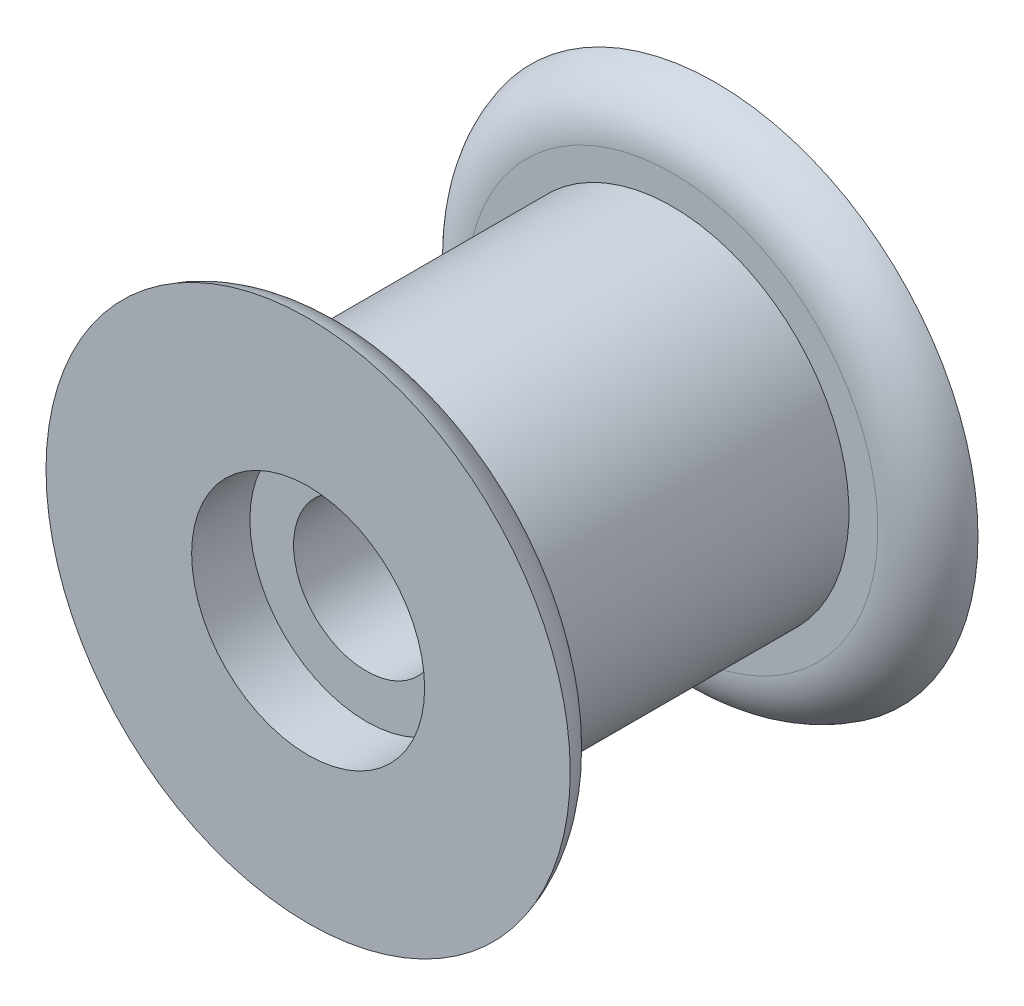
SolidWorks part; units mm, degrees
ref_plane "Front Plane" through (0, 0, 0) normal (0, 0, 1) x (1, 0, 0)
ref_plane "Top Plane" through (0, 0, 0) normal (0, 1, 0) x (1, 0, 0)
ref_plane "Right Plane" through (0, 0, 0) normal (1, 0, 0) x (0, 0, -1)
sketch "Sketch1" plane through (0, 0, 0) normal (0, 1, 0) x (1, 0, 0)
  line L0 (0, 0) -> (9, 0)
  line L1 (9, 0) -> (9, -1.5)
  line L2 (9, -1.5) -> (6.07, -1.5)
  line L3 (6.07, -1.5) -> (6.07, -12.5)
  line L4 (6.07, -12.5) -> (9, -12.5)
  line L5 (9, -12.5) -> (9, -14)
  line L6 (9, -14) -> (0, -14)
  line L7 (0, 9.9412) -> (0, -24.4941) construction
  line L8 (0, 0) -> (0, -14)
  dimension "D1" = 9
  dimension "D2" = 9
  dimension "D3" = 1.5
  dimension "D4" = 1.5
  dimension "D5" = 11
  dimension "D6" = 6.07
revolve "Revolve1" add sketch "Sketch1" angle 360 about L7
ref_plane "Plane1" through (0, 0, 7) normal (0, 0, -1) x (-1, 0, 0)
fillet "Fillet1" radius 2 2 edges at (-9, 0, 12.5) (-9, 0, 1.5)
sketch "Sketch2" plane through (0, 0, 0) normal (0, 0, -1) x (-1, 0, 0)
  circle A0 centre (0, 0) radius 4
extrude "Cut-Extrude2" cut sketch "Sketch2" against normal blind 2
mirror "Mirror1" about plane through (0, 0, 7) normal (0, 0, -1) of "Cut-Extrude2"
sketch "Sketch4" plane through (0, 0, 12) normal (0, 0, 1) x (1, 0, 0)
  circle A0 centre (0, 0) radius 2.5
extrude "Cut-Extrude3" cut sketch "Sketch4" against normal up to surface (10 mm away) up to face at (-4, 0, 2)
